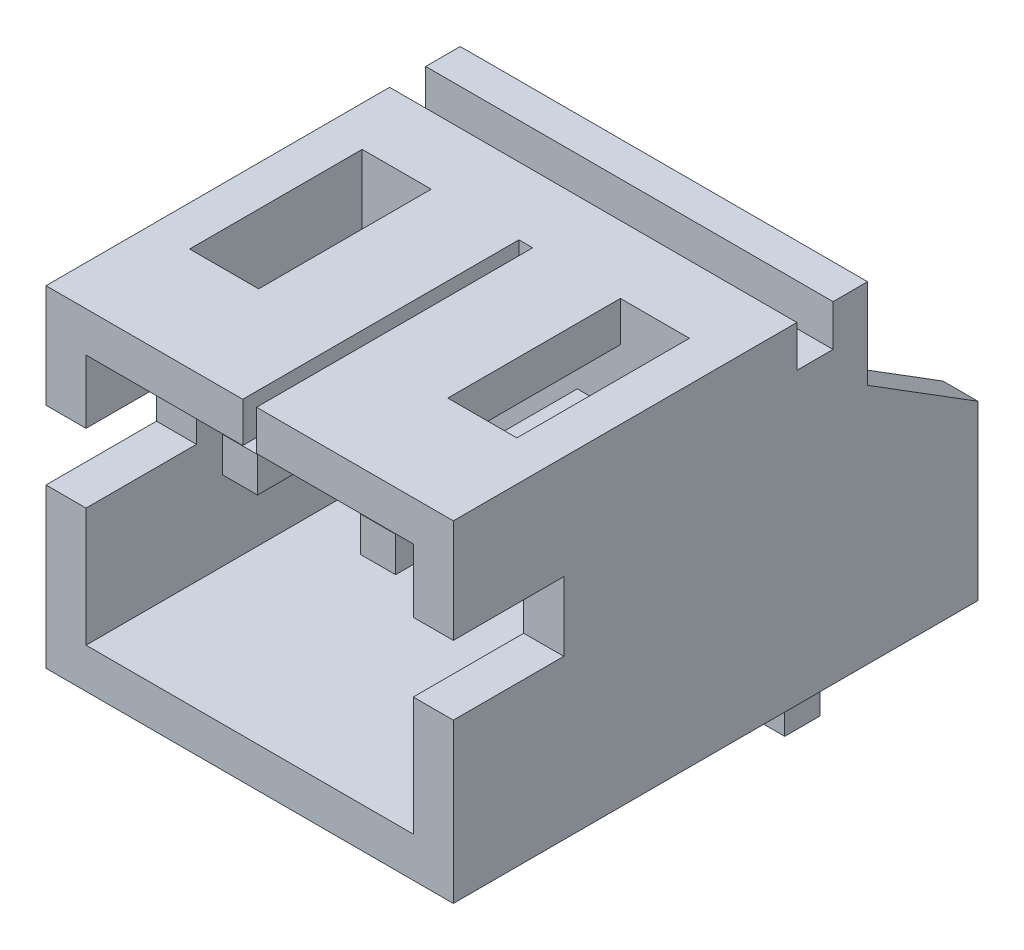
SolidWorks part; units mm, degrees
material "A-Glass Fiber"
ref_plane "Front Plane" through (0, 0, 0) normal (0, 0, 1) x (1, 0, 0)
ref_plane "Top Plane" through (0, 0, 0) normal (0, 1, 0) x (1, 0, 0)
ref_plane "Right Plane" through (0, 0, 0) normal (1, 0, 0) x (0, 0, -1)
sketch "Sketch4" plane through (6.8642, -1.8637, 0) normal (0, 0, 1) x (1, 0, 0)
  line L0 (-9.8142, 4.2637) -> (-3.9142, -0.5363) construction
  line L7 (-3.9142, 4.2637) -> (-9.8142, 4.2637)
  line L8 (-3.9142, 4.2637) -> (-3.9142, -0.5363)
  line L9 (-3.9142, -0.5363) -> (-9.8142, -0.5363)
  line L10 (-9.8142, 4.2637) -> (-9.8142, -0.5363)
  dimension "D4" = 5.9
  dimension "D7" = 4.8
extrude "Body-Extrude2" add sketch "Sketch4" along normal blind 6 separate body
shell "Body-Shell1" thickness 0.58 removed face at (0, 0, 6)
sketch "Sketch66" plane through (0, 1.82, 0) normal (0, 1, 0) x (1, 0, 0)
  line L1 (0.1, -6) -> (-0.1, -6)
  line L2 (0.1, -6) -> (0.1, -2)
  line L3 (0.1, -2) -> (-0.1, -2)
  line L4 (-0.1, -6) -> (-0.1, -2)
  line L7 (-1.37, -2) -> (-2.37, -2)
  line L8 (-1.37, -2) -> (-1.37, -4.5)
  line L9 (-1.37, -4.5) -> (-2.37, -4.5)
  line L10 (-2.37, -2) -> (-2.37, -4.5)
  line L13 (1.37, -2) -> (2.37, -2)
  line L14 (1.37, -2) -> (1.37, -4.5)
  line L15 (1.37, -4.5) -> (2.37, -4.5)
  line L16 (2.37, -2) -> (2.37, -4.5)
  line L17 (-2.37, -2) -> (2.37, -2) construction
  line L18 (-2.37, -6) -> (-2.37, -2) construction
  line L19 (2.37, -6) -> (2.37, -2) construction
  line L20 (-2.37, -6) -> (2.37, -6) construction
  line L21 (2.95, -6) -> (2.95, 0) construction
  point P7 (0, -2)
  dimension "D1" = 2.85
  dimension "D2" = 2.5
  dimension "D3" = 1
extrude "Extrude1" cut sketch "Sketch66" along normal up to next
sketch "Sketch6" plane through (2.95, 11.1173, 0) normal (1, 0, 0) x (0, 0, -1)
  line L0 (0, -10.0173) -> (1.6, -11.0173)
  line L1 (0, -13.5173) -> (0, -8.7173) construction
  line L2 (1.6, -11.0173) -> (1.6, -13.5173)
  line L3 (0, -13.5173) -> (1.6, -13.5173)
  line L4 (0, -10.0173) -> (0, -13.5173)
  line L5 (-6, -13.5173) -> (0, -13.5173) construction
  line L6 (-6, -8.7173) -> (0, -8.7173) construction
  dimension "D1" = 1.3
  dimension "D2" = 1.6
  dimension "D3" = 2.5
extrude "Tab-Extrude4" add sketch "Sketch6" against normal blind 0.508
sketch "Sketch9" plane through (-2.95, 11.1173, 0) normal (-1, 0, 0) x (0, 0, 1)
  line L4 (0, -13.5173) -> (0, -10.0173)
  line L5 (0, -13.5173) -> (0, -10.0173)
  line L7 (0, -10.0173) -> (-1.6, -11.0173)
  line L8 (-1.6, -11.0173) -> (-1.6, -13.5173)
  line L9 (-1.6, -13.5173) -> (0, -13.5173)
  line L11 (0, -10.0173) -> (-1.6, -11.0173)
  line L12 (-1.6, -11.0173) -> (-1.6, -13.5173)
  line L15 (-1.6, -13.5173) -> (0, -13.5173)
  dimension "D1" = 0
extrude "Tab-Extrude7" add sketch "Sketch9" against normal blind 0.508
ref_plane "Pins-Plane" through (0, 0, 5.14) normal (0, 0, 1) x (1, 0, 0)
sketch "Sketch64" plane through (0, 3.64, 5.14) normal (0, 0, -1) x (1, 0, 0)
  line L1 (-1.254, 3.194) -> (-0.746, 3.194)
  line L2 (-1.254, 3.194) -> (-1.254, 2.686)
  line L3 (-1.254, 2.686) -> (-0.746, 2.686)
  line L4 (-0.746, 3.194) -> (-0.746, 2.686)
  line L5 (-2.95, 1.24) -> (-2.95, 6.04) construction
  line L6 (2.95, 1.24) -> (0.1, 1.24) construction
  line L11 (-1.254, 3.194) -> (-0.746, 2.686) construction
  line L15 (-0.746, 2.94) -> (0, 2.94) construction
  point P8 (-1, 2.94)
  dimension "D1" = 1.7
  dimension "D2" = 0.508
  dimension "D3" = 1.95
sketch "Sketch65" plane through (0, 0, 0) normal (1, 0, 0) x (0, 0, -1)
  line L0 (-5.14, 0.7) -> (-0.25, 0.7)
  line L1 (0.75, -0.3) -> (0.75, -4.4)
  line L2 (0, 1.1) -> (0, 2.4) construction
  line L3 (-6, -2.4) -> (1.6, -2.4) construction
  arc A0 (-0.25, 0.7) -> (0.75, -0.3) centre (-0.25, -0.3) cw
  dimension "D3" = 1
  dimension "D1" = 0.75
  dimension "D2" = 2
sweep "Pins-Sweep" add profiles "Sketch64" path "Sketch65"
ref_point "Point1"
ref_axis "Axis1" through (-1, -5.3906, -0.75) along (0, 1, 0)
pattern_linear "Pins-LPattern" count 2 spacing 2 along (1, 0, 0) of "Pins-Sweep"
ref_plane "Plane1" through (2.95, 0, 0) normal (1, 0, 0) x (0, 0, -1)
sketch "Sketch67" plane through (2.95, 0, 0) normal (1, 0, 0) x (0, 0, -1)
  line L2 (-6, -2.4) -> (-6, 2.4) construction
  line L3 (-6, 0.9) -> (-4.4, 0.9)
  line L4 (-4.4, 0.9) -> (-4.4, -0.1)
  line L5 (-4.4, -0.1) -> (-6, -0.1)
  line L7 (-6, 0.9) -> (-6, -0.1)
extrude "Cut-Extrude2" cut sketch "Sketch67" against normal blind 1
mirror "Mirror1" about plane through (0, 0, 0) normal (1, 0, 0) of "Cut-Extrude2"
ref_plane "Plane2" through (0, 2.4, 0) normal (0, 1, 0) x (1, 0, 0)
sketch "Sketch68" plane through (0, 2.4, 0) normal (0, 1, 0) x (1, 0, 0)
  line L1 (-2.95, -6) -> (-2.95, 0) construction
  line L2 (-2.95, -0.5) -> (2.95, -0.5)
  line L3 (-2.95, -0.5) -> (-2.95, -1.0234)
  line L4 (-2.95, -1.0234) -> (2.95, -1.0234)
  line L5 (2.95, -0.5) -> (2.95, -1.0234)
  line L6 (2.95, -6) -> (2.95, 0) construction
  dimension "D1" = 0.5234
extrude "Cut-Extrude3" cut sketch "Sketch68" against normal blind 0.6
